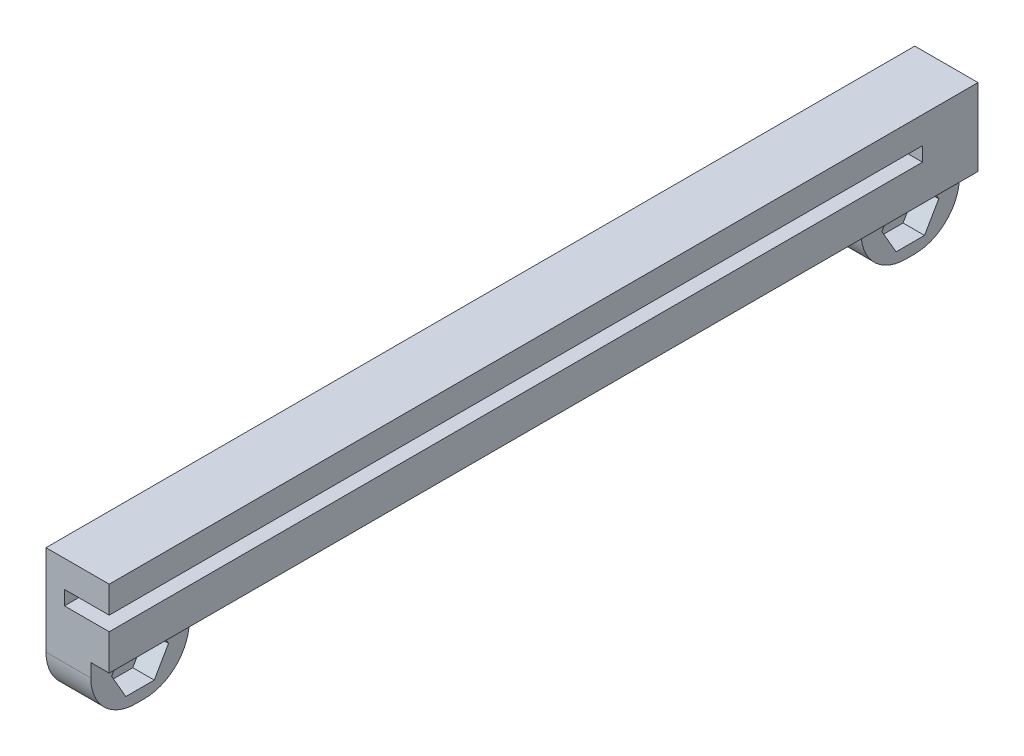
SolidWorks part; units mm, degrees
ref_plane "Front Plane" through (0, 0, 0) normal (0, 0, 1) x (1, 0, 0)
ref_plane "Top Plane" through (0, 0, 0) normal (0, 1, 0) x (1, 0, 0)
ref_plane "Right Plane" through (0, 0, 0) normal (1, 0, 0) x (0, 0, -1)
sketch "Sketch1" plane through (0, 0, 0) normal (0, 1, 0) x (1, 0, 0)
  line L1 (-3.5288, -48.5) -> (3.5288, -48.5)
  line L2 (-3.5288, -48.5) -> (-3.5288, 48.5)
  line L3 (-3.5288, 48.5) -> (3.5288, 48.5)
  line L4 (3.5288, -48.5) -> (3.5288, 48.5)
  line L5 (-3.5288, -48.5) -> (3.5288, 48.5) construction
  line L6 (-3.5288, 48.5) -> (3.5288, -48.5) construction
  point P0 (0, 0)
  dimension "D1" = 97
  dimension "D2" = 7.0575
extrude "Boss-Extrude2" add sketch "Sketch1" along normal blind 7.6
sketch "Sketch4" plane through (0, 7.6, 0) normal (0, 1, 0) x (1, 0, 0)
  line L0 (3.5288, -48.5) -> (3.5288, 48.5) construction
  line L1 (3.5288, 42.305) -> (-1.4713, 42.305)
  line L2 (3.5288, 42.305) -> (3.5288, -48.5)
  line L3 (3.5288, -48.5) -> (-1.4713, -48.5)
  line L4 (-1.4713, 42.305) -> (-1.4713, -48.5)
  line L5 (-3.5288, -48.5) -> (3.5288, -48.5) construction
  line L7 (-3.5288, 48.5) -> (-3.5288, -48.5) construction
  dimension "D1" = 90.805
  dimension "D2" = 2.0575
extrude "Cut-Extrude1" cut sketch "Sketch4" against normal blind 4.6
sketch "Sketch6" plane through (0, 7.6, 0) normal (0, 1, 0) x (1, 0, 0)
  line L1 (3.5288, 42.305) -> (-1.4713, 42.305)
  line L2 (3.5288, 42.305) -> (3.5288, -48.5)
  line L3 (3.5288, -48.5) -> (-1.4713, -48.5)
  line L4 (-1.4713, 42.305) -> (-1.4713, -48.5)
extrude "Boss-Extrude3" add sketch "Sketch6" against normal blind 3
sketch "Sketch8" plane through (0, 0, 0) normal (0, -1, 0) x (1, 0, 0)
  line L1 (-3.5288, 48.5) -> (3.5287, 48.5)
  line L2 (-3.5288, 48.5) -> (-3.5287, -48.5)
  line L3 (-3.5287, -48.5) -> (3.5288, -48.5)
  line L4 (3.5287, 48.5) -> (3.5288, -48.5)
extrude "Boss-Extrude4" add sketch "Sketch8" along normal blind 1
sketch "Sketch9" plane through (0, -1, 0) normal (0, -1, 0) x (1, 0, 0)
  line L1 (-3.5288, 48.5) -> (1.4712, 48.5)
  line L2 (-3.5288, 48.5) -> (-3.5288, 37.5)
  line L3 (-3.5288, 37.5) -> (1.4712, 37.5)
  line L4 (1.4712, 48.5) -> (1.4712, 37.5)
  line L5 (-3.5287, -48.5) -> (1.4713, -48.5)
  line L6 (-3.5287, -48.5) -> (-3.5287, -37.5)
  line L7 (-3.5287, -37.5) -> (1.4713, -37.5)
  line L8 (1.4713, -48.5) -> (1.4713, -37.5)
  point P10 (1.4713, -43)
  dimension "D1" = 11
  dimension "D2" = 11
  dimension "D3" = 5
  dimension "D4" = 5
extrude "Boss-Extrude5" add sketch "Sketch9" along normal blind 6.5 contours L2 L1 L4 L3 | L6 L5 L8 L7
sketch "Sketch10" plane through (1.4713, 0, 0) normal (1, 0, 0) x (0, 0, -1)
  line L0 (-48.5, -7.5) -> (-48.5, -1) construction
  line L1 (-44.5877, -0.75) -> (-46.1754, -3.5)
  line L2 (-46.1754, -3.5) -> (-44.5877, -6.25)
  line L3 (-44.5877, -6.25) -> (-41.4123, -6.25)
  line L4 (-41.4123, -6.25) -> (-39.8246, -3.5)
  line L5 (-39.8246, -3.5) -> (-41.4123, -0.75)
  line L6 (-41.4123, -0.75) -> (-44.5877, -0.75)
  line L7 (-48.5, -7.5) -> (-37.5, -7.5) construction
  line L8 (37.5, -7.5) -> (37.5, -1) construction
  line L9 (46.1754, -3.5) -> (44.5877, -0.75)
  line L10 (44.5877, -0.75) -> (41.4123, -0.75)
  line L11 (41.4123, -0.75) -> (39.8246, -3.5)
  line L12 (39.8246, -3.5) -> (41.4123, -6.25)
  line L13 (41.4123, -6.25) -> (44.5877, -6.25)
  line L14 (44.5877, -6.25) -> (46.1754, -3.5)
  line L15 (48.5, -7.5) -> (37.5, -7.5) construction
  circle A0 centre (-43, -3.5) radius 2.75 construction
  circle A1 centre (43, -3.5) radius 2.75 construction
  dimension "D1" = 5.5
  dimension "D2" = 5.5
  dimension "D3" = 1.25
  dimension "D4" = 5.5
  dimension "D5" = 1.25
  dimension "D6" = 5.5
extrude "Cut-Extrude2" cut sketch "Sketch10" against normal blind 2.4
sketch "Sketch11" plane through (-0.9287, 0, 0) normal (1, 0, 0) x (0, 0, -1)
  line L2 (-48.5, -7.5) -> (-37.5, -7.5) construction
  line L3 (-48.5, -7.5) -> (-48.5, -1) construction
  line L4 (37.5, -7.5) -> (37.5, -1) construction
  line L5 (48.5, -7.5) -> (37.5, -7.5) construction
  circle A0 centre (-43, -3.5) radius 1.5
  circle A1 centre (43, -3.5) radius 1.5
  dimension "D3" = 3
  dimension "D4" = 3
  dimension "D1" = 4
  dimension "D2" = 5.5
  dimension "D5" = 5.5
  dimension "D6" = 4
extrude "Cut-Extrude3" cut sketch "Sketch11" against normal through all contours A0 | A1
fillet "Fillet2" radius 5 4 edges at (-1.0287, -7.5, -48.5) (-1.0287, -7.5, -37.5) (-1.0288, -7.5, 37.5) (-1.0288, -7.5, 48.5)
mirror "Mirror2" [suppressed] of bodies 109
delete or keep bodies "Body-Delete/Keep 1" [suppressed] type delete bodies bodies 109
